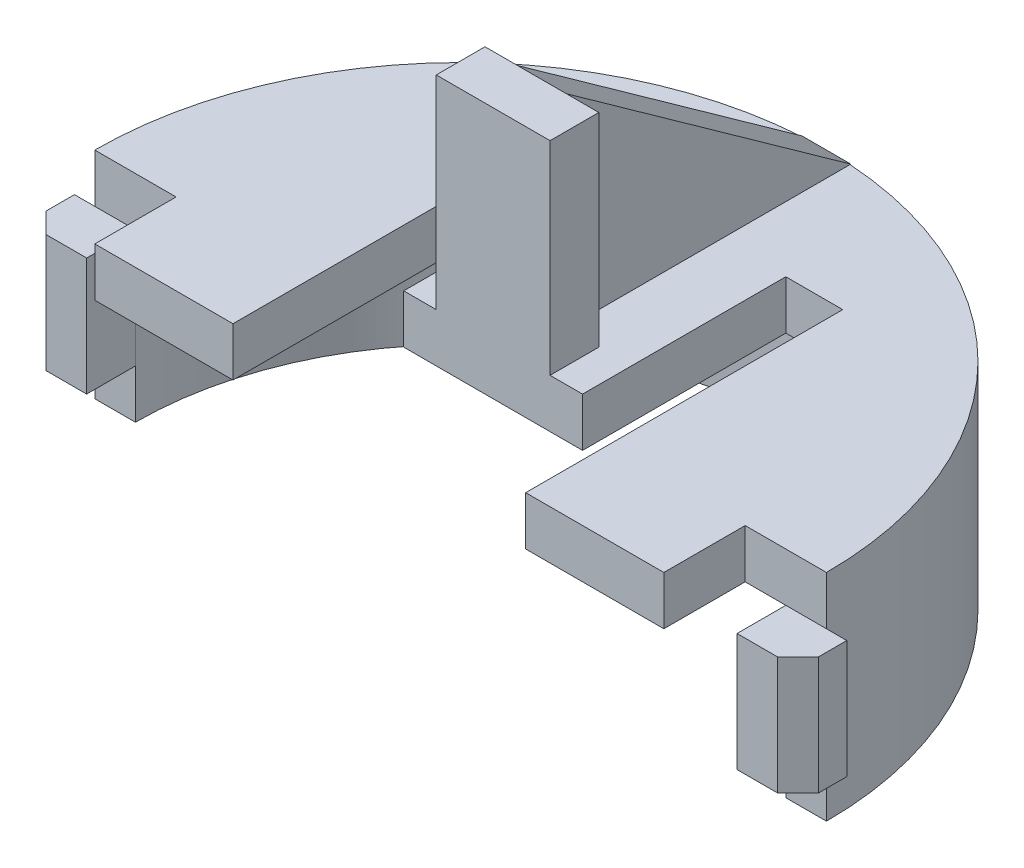
SolidWorks part; units mm, degrees
ref_plane "Front Plane" through (0, 0, 0) normal (0, 0, 1) x (1, 0, 0)
ref_plane "Top Plane" through (0, 0, 0) normal (0, 1, 0) x (1, 0, 0)
ref_plane "Right Plane" through (0, 0, 0) normal (1, 0, 0) x (0, 0, -1)
sketch "Sketch1" plane through (0, 0, 0) normal (0, 0, 1) x (1, 0, 0)
  line L0 (0, 0) -> (9, 0)
  line L1 (9, 0) -> (9, 5.3)
  line L2 (9, 5.3) -> (8, 5.3)
  line L3 (8, 5.3) -> (8, 0)
  line L4 (9, 4.1) -> (0, 4.1)
  line L5 (0, 4.1) -> (0, 5.3)
  line L6 (0, 5.3) -> (8, 5.3)
  line L7 (0, 0) -> (0, 2.65) construction
  dimension "D1" = 9
  dimension "D2" = 5.3
  dimension "D3" = 1
  dimension "D4" = 1.2
revolve "Revolve1" add sketch "Sketch1" angle 180 about L7 region at (8.5, 2.05, 0) region at (4, 4.7, 0) region at (8.5, 4.7, 0)
sketch "Sketch2" plane through (0, 0, 0) normal (0, 0, 1) x (1, 0, 0)
  line L0 (-8, 4.1) -> (8, 4.1) construction
  line L1 (-3.105, 4.1) -> (3.105, 4.1)
  line L2 (-3.105, 4.1) -> (-3.105, 2.6)
  line L3 (-3.105, 2.6) -> (3.105, 2.6)
  line L4 (3.105, 4.1) -> (3.105, 2.6)
  line L5 (-3.105, 4.1) -> (3.105, 2.6) construction
  line L6 (-3.105, 2.6) -> (3.105, 4.1) construction
  point P0 (0, 3.35)
  point P5 (0, 0)
  dimension "D1" = 6.21
  dimension "D2" = 1.5
  dimension "D3" = 0
  dimension "D4" = 0
extrude "Cut-Extrude1" cut sketch "Sketch2" against normal through all
sketch "Sketch3" plane through (0, 5.3, 0) normal (0, 1, 0) x (1, 0, 0)
  line L0 (9, 0) -> (-9, 0) construction
  line L1 (-3.6, 5.8) -> (3.6, 5.8)
  line L2 (-3.6, 5.8) -> (-3.6, 0)
  line L3 (-3.6, 0) -> (3.6, 0)
  line L4 (3.6, 5.8) -> (3.6, 0)
  line L5 (-3.6, 5.8) -> (3.6, 0) construction
  line L6 (-3.6, 0) -> (3.6, 5.8) construction
  line L8 (-2.2, 5.8) -> (2.2, 5.8)
  line L9 (-2.2, 5.8) -> (-2.2, 0.8)
  line L10 (-2.2, 0.8) -> (2.2, 0.8)
  line L11 (2.2, 5.8) -> (2.2, 0.8)
  line L12 (-2.2, 5.8) -> (2.2, 0.8) construction
  line L13 (-2.2, 0.8) -> (2.2, 5.8) construction
  point P0 (0, 2.9)
  point P8 (0, 3.3)
  line M9 (-9, 0) -> (9, 0)
  dimension "D1" = 7.2
  dimension "D2" = 5.8
  dimension "D3" = 0
  dimension "D4" = 0
  dimension "D5" = 4.4
  dimension "D6" = 5
  dimension "D7" = 0
  dimension "D8" = 0
extrude "Cut-Extrude2" cut sketch "Sketch3" against normal through all contours L1 L11 L10 L9 L2 L4 M9 region at (-2.9, 5.3, -5.7075)
sketch "Sketch4" plane through (0, 5.3, 0) normal (0, 1, 0) x (1, 0, 0)
  line L1 (3.6, 0) -> (7, 0)
  line L2 (3.6, 0) -> (3.6, -2)
  line L3 (3.6, -2) -> (7, -2)
  line L4 (7, 0) -> (7, -2)
  line L5 (-3.6, 0) -> (-7, 0)
  line L6 (-3.6, 0) -> (-3.6, -2)
  line L7 (-3.6, -2) -> (-7, -2)
  line L8 (-7, 0) -> (-7, -2)
  dimension "D1" = 3.4
  dimension "D2" = 3.4
  dimension "D3" = 2
  dimension "D4" = 2
extrude "Boss-Extrude1" add sketch "Sketch4" against normal blind 1.2
ref_plane "Plane1" through (8, 0, 0) normal (1, 0, 0) x (0, 0, -1)
sketch "Sketch5" plane through (8, 0, 0) normal (1, 0, 0) x (0, 0, -1)
  line L0 (0, 0) -> (0, 5.3) construction
  line L1 (0, 4.1) -> (-1.2, 4.1)
  line L2 (0, 4.1) -> (0, 1.2)
  line L3 (0, 1.2) -> (-1.2, 1.2)
  line L4 (-1.2, 4.1) -> (-1.2, 1.2)
  line L5 (-1.2, 4.1) -> (0, 1.2) construction
  line L6 (0, 4.1) -> (-1.2, 1.2) construction
  point P6 (-0.6, 2.65)
  dimension "D1" = 2.65
  dimension "D2" = 2.9
  dimension "D3" = 1.2
extrude "Boss-Extrude2" add sketch "Sketch5" along normal blind 1.5
chamfer "Chamfer1" distance 0.5 angle 45 1 edges at (9.5, 2.65, 1.2)
mirror "Mirror2" about plane through (0, 0, 0) normal (1, 0, 0) of "Boss-Extrude2", "Chamfer1"
sketch "Sketch6" plane through (0, 0, -0.8) normal (0, 0, 1) x (1, 0, 0)
  line L0 (-2.2, 5.3) -> (2.2, 5.3) construction
  line L1 (1.4, 5.3) -> (-1.4, 5.3)
  line L2 (1.4, 5.3) -> (1.4, 10.3)
  line L3 (1.4, 10.3) -> (-1.4, 10.3)
  line L4 (-1.4, 5.3) -> (-1.4, 10.3)
  line L5 (-1.4, 10.3) -> (1.4, 5.3) construction
  line L6 (-1.4, 5.3) -> (1.4, 10.3) construction
  point P6 (0, 7.8)
  dimension "D1" = 0
  dimension "D2" = 5
  dimension "D3" = 2.8
extrude "Boss-Extrude3" add sketch "Sketch6" against normal blind 1.2 contours L4 L3 L2 L1
sketch "Sketch7" plane through (0, 0, 0) normal (1, 0, 0) x (0, 0, -1)
  line L0 (2, 10.3) -> (9, 5.3)
  line L1 (9, 5.3) -> (0, 5.3) construction
  line L2 (9, 5.3) -> (2, 5.3)
  line L3 (2, 5.3) -> (2, 10.3)
extrude "Boss-Extrude4" add sketch "Sketch7" along normal mid plane 1.2
